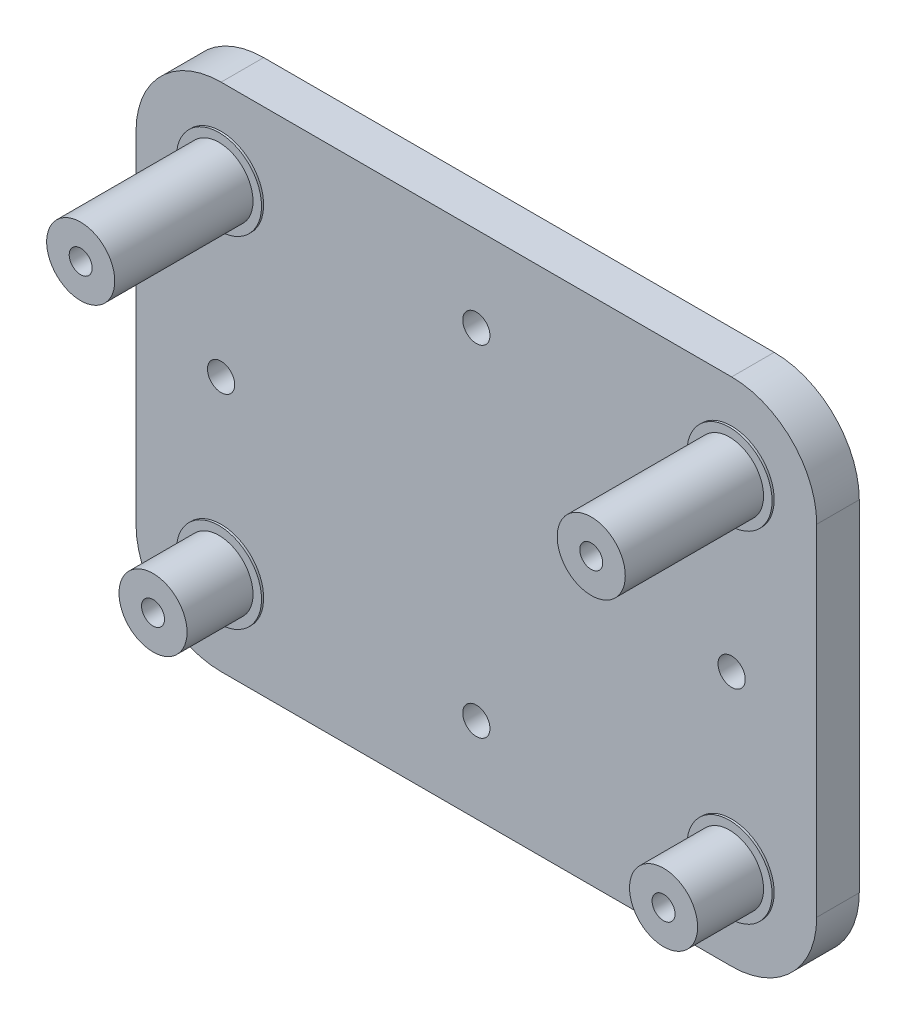
SolidWorks part; units mm, degrees
ref_plane "Front Plane" through (0, 0, 0) normal (0, 0, 1) x (1, 0, 0)
ref_plane "Top Plane" through (0, 0, 0) normal (0, 1, 0) x (1, 0, 0)
ref_plane "Right Plane" through (0, 0, 0) normal (1, 0, 0) x (0, 0, -1)
ref_axis "X" through (-88.99, 0, 0) along (1, 0, 0)
ref_axis "Y" through (0, 55, 0) along (0, -1, 0)
ref_axis "Z" through (0, 0, -88.99) along (0, 0, 1)
sketch "Sketch1" plane through (0, 0, 0) normal (0, 0, 1) x (1, 0, 0)
  line L1 (-30, 20) -> (30, 20) construction
  line L2 (-30, 20) -> (-30, -20) construction
  line L3 (-30, -20) -> (30, -20) construction
  line L4 (30, 20) -> (30, -20) construction
  line L5 (-30, 20) -> (30, -20) construction
  line L6 (-30, -20) -> (30, 20) construction
  line L7 (-40, 30) -> (40, 30)
  line L8 (-40, 30) -> (-40, -30)
  line L9 (-40, -30) -> (40, -30)
  line L10 (40, 30) -> (40, -30)
  line L11 (-40, 30) -> (40, -30) construction
  line L12 (-40, -30) -> (40, 30) construction
  circle A0 centre (-30, 20) radius 4
  circle A1 centre (-30, -20) radius 4
  circle A2 centre (30, -20) radius 4
  circle A3 centre (30, 20) radius 4
  circle A4 centre (-30, 20) radius 5
  circle A5 centre (30, 20) radius 5
  circle A6 centre (30, -20) radius 5
  circle A7 centre (-30, -20) radius 5
  circle A8 centre (-30, 20) radius 1.35
  circle A9 centre (-30, -20) radius 1.35
  circle A10 centre (30, 20) radius 1.35
  circle A11 centre (30, -20) radius 1.35
  circle A12 centre (-30, 0) radius 1.6
  circle A13 centre (0, 20) radius 1.6
  circle A14 centre (30, 0) radius 1.6
  circle A15 centre (0, -20) radius 1.6
  point P0 (0, 0)
  point P10 (0, 0)
  dimension "D1" = 40
  dimension "D3" = 8
  dimension "D6" = 1
  dimension "D7" = 2.7
  dimension "D8" = 3.2
  dimension "D2" = 60
  dimension "D4" = 10
  dimension "D5" = 10
extrude "Boss-Extrude1" add sketch "Sketch1" against normal blind 5 contours L8 L9 L10 L7
extrude "Boss-Extrude2" add sketch "Sketch1<3>" along normal blind 8 contours A1 A9 | A2 A11 region at (-33.8869, -20, 0) region at (26.1131, -20, 0)
sketch "Sketch1<3>" plane through (0, 0, 0) normal (0, 0, 1) x (1, 0, 0) same geometry as "Sketch1"
extrude "Boss-Extrude4" add sketch "Sketch1<5>" along normal blind 16.5 contours A0 A8 | A3 A10 region at (-33.8869, 20, 0) region at (26.1131, 20, 0)
sketch "Sketch1<5>" plane through (0, 0, 0) normal (0, 0, 1) x (1, 0, 0) same geometry as "Sketch1"
extrude "Boss-Extrude3" add sketch "Sketch1<4>" along normal blind 0.25 contours A4 A0 | A5 A3 | A6 A2 | A7 A1 region at (-34.8586, 20, 0) region at (25.1414, 20, 0) region at (25.1414, -20, 0) region at (-34.8586, -20, 0)
sketch "Sketch1<4>" plane through (0, 0, 0) normal (0, 0, 1) x (1, 0, 0) same geometry as "Sketch1"
extrude "Cut-Extrude1" cut sketch "Sketch1<6>" against normal through all both and the other way through all contours A13 | A12 | A15 | A14 region at (-30, 0, 0) region at (0, 20, 0) region at (30, 0, 0) region at (0, -20, 0)
sketch "Sketch1<6>" plane through (0, 0, 0) normal (0, 0, 1) x (1, 0, 0) same geometry as "Sketch1"
fillet "Fillet1" radius 10 4 edges at (40, 30, -2.5) (40, -30, -2.5) (-40, -30, -2.5) (-40, 30, -2.5)
